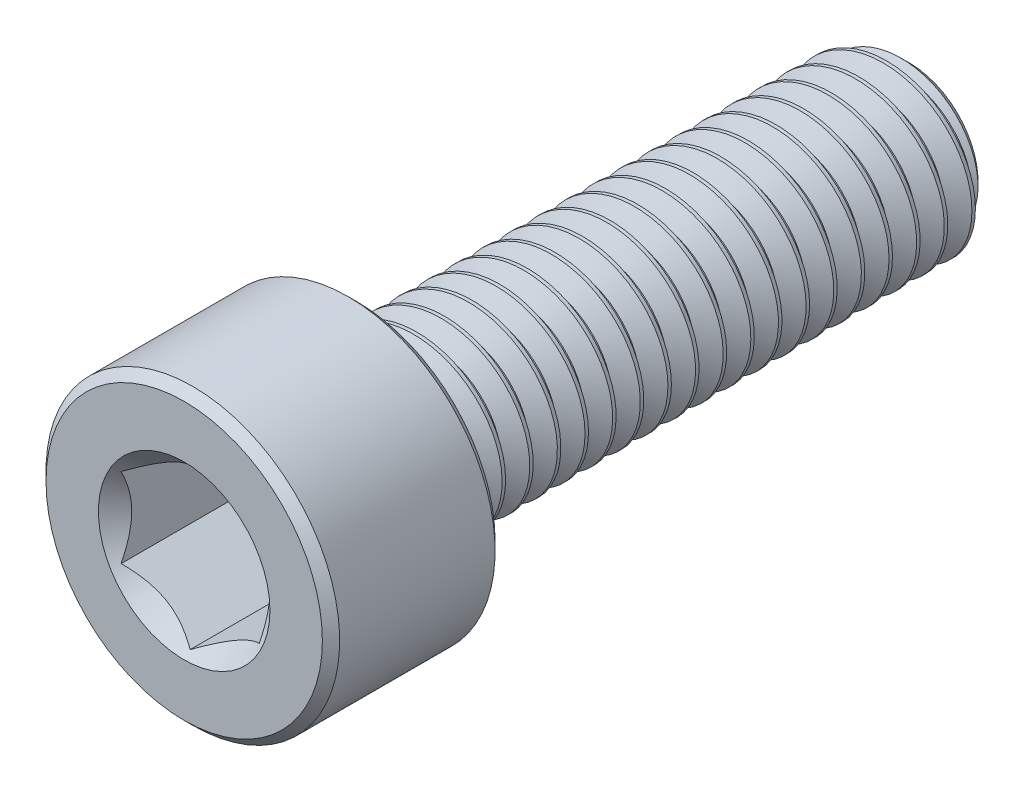
SolidWorks part; units mm, degrees
ref_plane "Front Plane" through (0, 0, 0) normal (0, 0, 1) x (1, 0, 0)
ref_plane "Top Plane" through (0, 0, 0) normal (0, 1, 0) x (1, 0, 0)
ref_plane "Right Plane" through (0, 0, 0) normal (1, 0, 0) x (0, 0, -1)
sketch "Sketch1" plane through (0, 0, 0) normal (1, 0, 0) x (0, 0, -1)
  line L0 (-10.5, 0) -> (10.5, 0) construction
  line L1 (10.5, 0) -> (10.5, 1.9804) construction
  line L2 (10.5, 1.9804) -> (9.9804, 2.5) construction
  line L3 (9.9804, 2.5) -> (9.9, 2.5) construction
  line L4 (9.9, 2.5) -> (-5.5, 2.5) construction
  line L5 (-5.5, 2.5) -> (-5.5, 4.25) construction
  line L6 (-5.5, 4.25) -> (-10.5, 4.25) construction
  line L7 (-10.5, 4.25) -> (-10.5, 0) construction
  line L8 (10.5, 1.9804) -> (10.5, 2.5) construction
  line L9 (10.45, 2.5866) -> (10.85, 1.8938) construction
  line L10 (10.85, 1.8938) -> (11.25, 2.5866) construction
  line L11 (11.25, 2.5866) -> (10.45, 2.5866) construction
  line L12 (10.85, 2.5866) -> (10.85, 2.5) construction
  line L13 (10.85, 1.8938) -> (10.85, 1.9804) construction
  line L14 (10.8, 1.9804) -> (10.9, 1.9804) construction
  line L15 (10.5, 2.5) -> (11.2, 2.5) construction
  line L16 (10.475, 2.5433) -> (11.225, 2.5433) construction
  line L17 (10.5, 0) -> (10.5, -2.5) construction
  line L18 (-5.75, 4.25) -> (-5.5, 4) construction
  line L19 (-10.25, 4.25) -> (-10.5, 4) construction
  line L20 (-5.5, 2.5) -> (-5.5, 0) construction
  line L21 (-5.5, 1.25) -> (-0.1667, 1.25) construction
  line L22 (-0.1667, 1.25) -> (5.1667, 1.25) construction
  line L23 (5.1667, 1.25) -> (10.5, 1.25) construction
  line L24 (-0.1667, 1.25) -> (-0.1667, 2.5) construction
  line L25 (-0.1667, 2.5) -> (-0.1667, 4.25) construction
  line L26 (5.1667, 1.25) -> (5.1667, 4.25) construction
  point P0 (-10.5, 2)
  point P3 (8.5, 2.5)
  point P4 (0, 0)
  point P18 (5.1667, 2.5)
  point P22 (10.85, 1.9804)
  point P24 (9.9, 2.5)
  point P25 (10.85, 2.5)
  point P28 (10.85, 2.5433)
  point P29 (8.5, -2.5)
  point P30 (-0.1667, 2.5)
  point P31 (-8, 4.25)
  point P37 (-6.375, 4.25)
  point P38 (-10.125, 4.25)
  point P45 (-0.1667, 1.25)
  point P46 (5.1667, 1.25)
  dimension "D2" = 0.1
  dimension "D7" = 0.25
  dimension "D8" = 0.25
  dimension "D9" = 0.25
  dimension "D10" = 0.125
  dimension "D11" = 0.625
  dimension "Drive Size" = 4
  dimension "Head Diameter" = 8.5
  dimension "Head Height" = 5
  dimension "Thread Pitch" = 0.8
  dimension "Thread Size" = 5
  dimension "Length" = 16
  dimension "D12" = 0.6
  dimension "D4" = 2
  dimension "D3" = 45
sketch "Sketch2" plane through (0, 0, 0) normal (1, 0, 0) x (0, 0, -1)
  line L0 (-10.5, 0) -> (-10.5, 4)
  line L1 (-10.25, 4.25) -> (-5.75, 4.25)
  line L2 (-5.5, 4) -> (-5.5, 2.75)
  line L4 (9.9804, 2.5) -> (10.5, 1.9804)
  line L5 (10.5, 1.9804) -> (10.5, 0)
  line L6 (-5.5, 4.25) -> (-10.5, 4.25) construction
  line L7 (10.5, 0) -> (-10.5, 0)
  line L8 (-10.25, 4.25) -> (-10.5, 4) construction
  line L10 (-10.25, 4.25) -> (-10.5, 4)
  line L14 (-5.75, 4.25) -> (-5.5, 4) construction
  line L16 (-5.75, 4.25) -> (-5.5, 4)
  line L17 (-5.5, 2.5) -> (-5.5, 4.25) construction
  line L19 (-5.25, 2.5) -> (9.9804, 2.5)
  line L20 (9.9, 2.5) -> (-5.5, 2.5) construction
  arc A1 (-5.5, 2.75) -> (-5.25, 2.5) centre (-5.25, 2.75) ccw
  dimension "D3" = 0.25
revolve "Revolve1" add sketch "Sketch2" angle 360 about L7
sketch "Sketch3" plane through (0, 0, 10.5) normal (0, 0, 1) x (1, 0, 0)
  line L1 (2, -1.1547) -> (2, 1.1547)
  line L2 (2, 1.1547) -> (0, 2.3094)
  line L3 (0, 2.3094) -> (-2, 1.1547)
  line L4 (-2, 1.1547) -> (-2, -1.1547)
  line L5 (-2, -1.1547) -> (0, -2.3094)
  line L6 (0, -2.3094) -> (2, -1.1547)
  circle A0 centre (0, 0) radius 2 construction
  circle A1 centre (0, 0) radius 4.25 construction
  circle A2 centre (0, 0) radius 4.25 construction
  circle A3 centre (0, 0) radius 2.3094 construction
  point P13 (0, 0)
  dimension "D1" = 4.6188
extrude "Cut-Extrude1" cut sketch "Sketch3" against normal offset from surface (4 mm away) 1 up to face at (0, 4, 5.5)
sketch "Sketch4" plane through (0, 0, 10.5) normal (0, 0, 1) x (1, 0, 0)
  circle A0 centre (0, 0) radius 2.4826
  dimension "D1" = 4.9652
extrude "Cut-Extrude2" cut sketch "Sketch4" against normal up to vertex (2.5 mm away) draft 45 up to point (0, 4.25, 8)
sketch "Sketch11" plane through (0, 0, 0) normal (1, 0, 0) x (0, 0, -1)
  line L0 (-10.5, 0) -> (10.5, 0) construction
  line L1 (-10.5, 0) -> (10.5, 0) construction
  line L2 (-2.5, 0) -> (-2.5, 2.5) construction
  line L3 (9.9, 2.5) -> (-5.5, 2.5) construction
  line L4 (7.5, 0) -> (7.5, 2.5) construction
  line L6 (10.5, 1.9804) -> (10.5, 2.5) construction
  point P2 (-2.5, 0)
  point P3 (7.5, 0)
  dimension "D1" = 3
  dimension "D2" = 3
sketch "Sketch6" plane through (0, 0, -10.5) normal (0, 0, -1) x (-1, 0, 0)
  circle A0 centre (0, 0) radius 2.5
curve "Helix/Spiral1" pitch 0.8 height 16.8 turns 21
sketch "Sketch10" plane through (0, 0, 0) normal (1, 0, 0) x (0, 0, -1)
  line L0 (-5.25, -4.25) -> (-5.25, 4.25)
  line L5 (-10.5, 0) -> (10.5, 0) construction
  line L6 (-5.25, 2.5) -> (-5.25, -2.5) construction
  point P3 (-5.25, 0)
split "Split1" trim tools "Sketch10" bodies to split 106 resulting bodies 114 115
sketch "Sketch7" plane through (0, 0, 0) normal (1, 0, 0) x (0, 0, -1)
  line L0 (10.475, 2.5433) -> (11.225, 2.5433)
  line L1 (11.225, 2.5433) -> (10.9, 1.9804)
  line L2 (10.9, 1.9804) -> (10.8, 1.9804)
  line L3 (10.8, 1.9804) -> (10.475, 2.5433)
sweep "Cut-Sweep1" cut profiles "Sketch7" path "Helix/Spiral1" align with end faces yes
sketch "Sketch8" plane through (0, 0, 0) normal (1, 0, 0) x (0, 0, -1)
  line L0 (-5.5, 0) -> (-5.5, 2.5)
  line L1 (-5.25, -2.5) -> (-5.25, 2.5) construction
  line L2 (-5.5, 2.5) -> (-5.25, 2.5)
  line L4 (-5.25, 2.5) -> (-3.8066, 0)
  line L5 (-3.8066, 0) -> (-5.5, 0)
  line L6 (9.9, 2.5) -> (-5.5, 2.5) construction
  line L7 (-10.5, 0) -> (10.5, 0) construction
  dimension "D1" = 60
revolve "Revolve2" add sketch "Sketch8" angle 360 about L5
equation "\"D2@Sketch1\" = \"Thread Pitch@Sketch1\" / 8"
equation "\"D4@Helix/Spiral1\" = \"Thread Pitch@Sketch1\""
equation "\"D7@Sketch1\" = \"Head Height@Sketch1\" * .05"
equation "\"D8@Sketch1\"=\"D7@Sketch1\""
equation "\"D9@Sketch1\"=\"D7@Sketch1\""
equation "\"D10@Sketch1\"=\"D7@Sketch1\"/2"
equation "\"D11@Sketch1\"=\"D10@Sketch1\"*5"
equation "\"D4@Sketch1\"=\"Thread Pitch@Sketch1\"*2.5"
equation "\"D12@Sketch1\"=\"Thread Pitch@Sketch1\"*.75"
equation "\"D3@Helix/Spiral1\"=\"Length@Sketch1\"+\"Thread Pitch@Sketch1\""
equation "\"D3@Sketch2\"=\"Thread Size@Sketch1\"*0.05"
equation "\"D1@Sketch11\"=\"Length@Sketch1\"*0.1875"
equation "\"D2@Sketch11\"=\"D1@Sketch11\""
equation "\"D1@Sketch4\"=\"D1@Sketch3\"*1.075"
